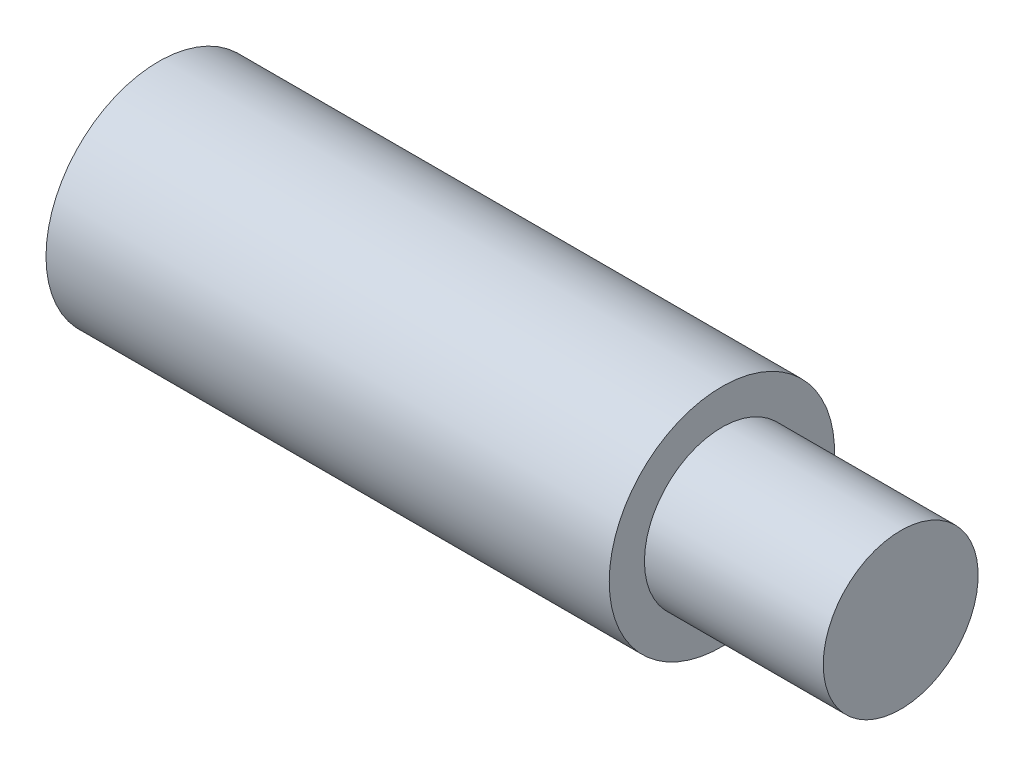
SolidWorks part; units mm, degrees
ref_plane "Front Plane" through (0, 0, 0) normal (0, 0, 1) x (1, 0, 0)
ref_plane "Top Plane" through (0, 0, 0) normal (0, 1, 0) x (1, 0, 0)
ref_plane "Right Plane" through (0, 0, 0) normal (1, 0, 0) x (0, 0, -1)
sketch "Fill_QC4 Sketch" plane through (0, 0, 0) normal (0, 0, 1) x (1, 0, 0)
  line L0 (-1000, 0) -> (1000, 0) construction
  line L1 (12.7, 0) -> (12.7, 5.5)
  line L2 (12.7, 5.5) -> (0, 5.5)
  line L3 (0, 5.5) -> (0, 8)
  line L4 (0, 8) -> (-40, 8)
  line L5 (-40, 8) -> (-40, 0)
  line L6 (-40, 0) -> (12.7, 0)
revolve "Fill_QC4" add sketch "Fill_QC4 Sketch" angle 360 about L0
ref_axis "Engine Axis" through (15.335, 0, 0) along (-1, 0, 0)
